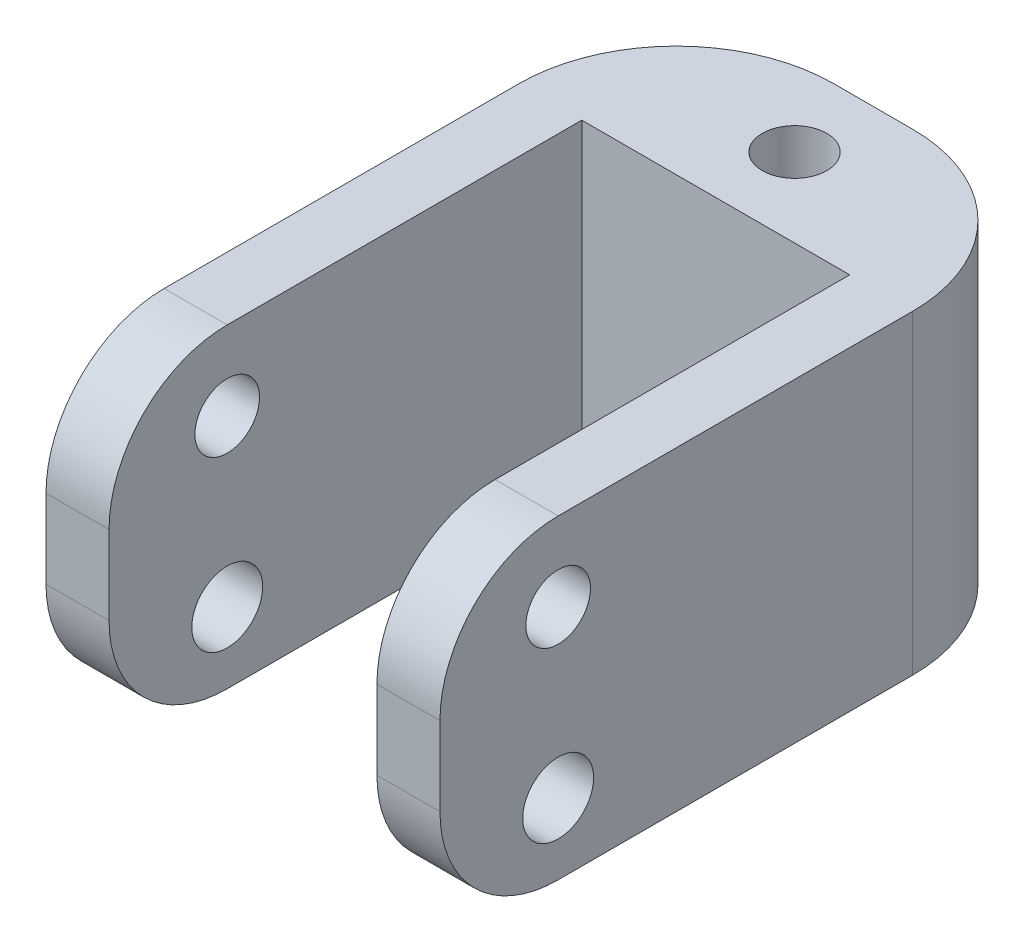
SolidWorks part; units mm, degrees
ref_plane "Front Plane" through (0, 0, 0) normal (0, 0, 1) x (1, 0, 0)
ref_plane "Top Plane" through (0, 0, 0) normal (0, 1, 0) x (1, 0, 0)
ref_plane "Right Plane" through (0, 0, 0) normal (1, 0, 0) x (0, 0, -1)
sketch "Sketch4" plane through (0, 0, 0) normal (1, 0, 0) x (0, 0, -1)
  line L1 (-40, -20) -> (40, -20)
  line L2 (-40, -20) -> (-40, 20)
  line L3 (-40, 20) -> (40, 20)
  line L4 (40, -20) -> (40, 20)
  line L5 (-40, -20) -> (40, 20) construction
  line L6 (-40, 20) -> (40, -20) construction
  line L7 (-25, 10) -> (-25, -11) construction
  circle A0 centre (-25, 10) radius 4.1
  circle A1 centre (-25, -11) radius 4.5
  circle A2 centre (-25, 10) radius 21 construction
  point P0 (0, 0)
  dimension "D3" = 8.2
  dimension "D4" = 10
  dimension "D5" = 15
  dimension "D6" = 9
  dimension "D7" = 42
  dimension "D1" = 40
  dimension "D2" = 80
extrude "Boss-Extrude2" add sketch "Sketch4" along normal mid plane 50
sketch "Sketch5" plane through (0, 0, 0) normal (0, 1, 0) x (1, 0, 0)
  line L0 (25, -40) -> (-25, -40) construction
  line L1 (-17, -40) -> (17, -40)
  line L2 (-17, -40) -> (-17, 20)
  line L3 (-17, 20) -> (17, 20)
  line L4 (17, -40) -> (17, 20)
  line L5 (0, 0) -> (0, -40) construction
  line L6 (15, -16.7956) -> (15, -59.1309) construction
  dimension "D1" = 2
  dimension "D2" = 60
extrude "Cut-Extrude3" cut sketch "Sketch5" against normal through all both and the other way through all
sketch "Sketch6" plane through (0, 0, 0) normal (0, 1, 0) x (1, 0, 0)
  line L0 (25, 40) -> (-25, 40) construction
  line L1 (0, 0) -> (0, 30) construction
  circle A0 centre (0, 30) radius 4.1
  dimension "D1" = 8.2
  dimension "D2" = 10
extrude "Cut-Extrude4" cut sketch "Sketch6" against normal through all both and the other way through all
fillet "Fillet1" radius 20 2 edges at (-25, 0, -40) (25, 0, -40)
fillet "Fillet3" radius 15 4 edges at (-21, 20, 40) (-21, -20, 40) (21, -20, 40) (21, 20, 40)
